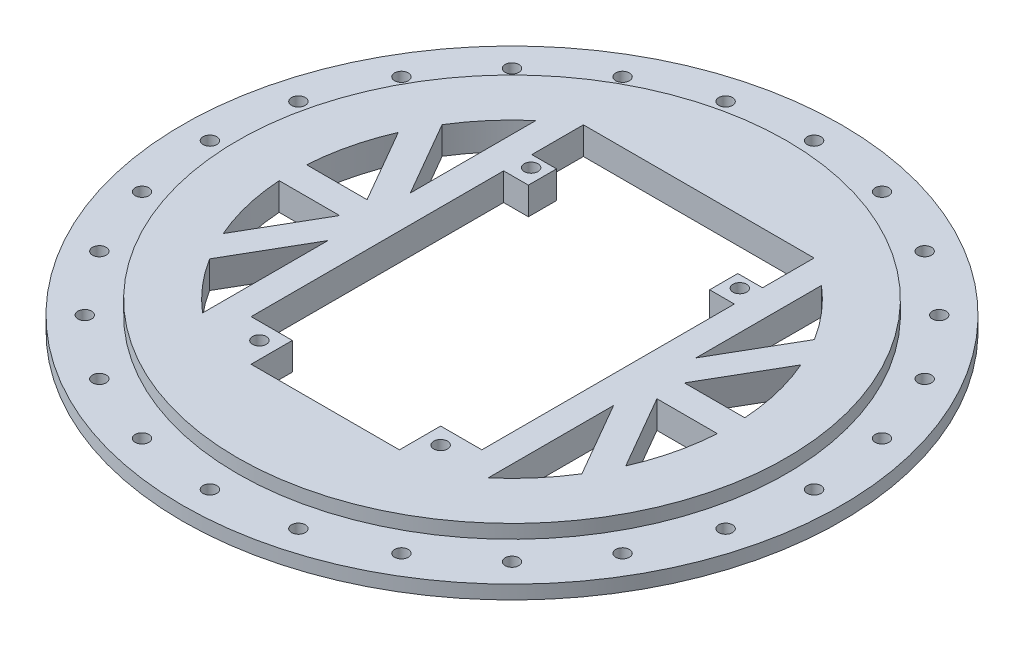
SolidWorks part; units mm, degrees
material "Acrylic (Medium-high impact)"
ref_plane "Front Plane" through (0, 0, 0) normal (0, 0, 1) x (1, 0, 0)
ref_plane "Top Plane" through (0, 0, 0) normal (0, 1, 0) x (1, 0, 0)
ref_plane "Right Plane" through (0, 0, 0) normal (1, 0, 0) x (0, 0, -1)
sketch "Sketch1" plane through (0, 0, 0) normal (0, 1, 0) x (1, 0, 0)
  line L0 (-33.02, -38.5419) -> (-33.02, -9.525)
  line L1 (-17.145, -43.18) -> (17.145, -43.18)
  line L2 (20.955, 31.2547) -> (26.67, 31.2547)
  line L3 (-26.67, 43.18) -> (26.67, 43.18)
  line L4 (17.145, -33.6423) -> (26.67, -33.6423)
  line L5 (33.02, -38.5419) -> (33.02, -9.525)
  line L6 (-33.02, -33.6423) -> (-33.02, 24.7396) construction
  line L7 (26.67, -33.6423) -> (26.67, 24.7396)
  line L8 (20.955, 24.7396) -> (26.67, 24.7396)
  line L9 (20.955, 24.7396) -> (20.955, 31.2547)
  line L10 (33.02, -33.6423) -> (33.02, 24.7396) construction
  line L11 (-33.02, 9.525) -> (-33.02, 38.5419)
  line L12 (33.02, 9.525) -> (33.02, 38.5419)
  line L14 (-36.6862, 3.175) -> (-50.7524, 3.175)
  line L15 (-36.6862, -3.175) -> (-50.7524, -3.175)
  line L16 (-26.67, -33.6423) -> (-17.145, -33.6423)
  line L17 (-17.145, -43.18) -> (-17.145, -33.6423)
  line L18 (17.145, -43.18) -> (17.145, -33.6423)
  line L19 (-26.67, 31.2547) -> (-20.955, 31.2547)
  line L20 (36.6862, 3.175) -> (50.7524, 3.175)
  line L21 (36.6862, -3.175) -> (50.7524, -3.175)
  line L22 (20.955, -37.4523) -> (20.955, 28.5496) construction
  line L23 (-26.67, 24.7396) -> (-20.955, 24.7396)
  line L24 (26.67, 31.2547) -> (26.67, 43.18)
  line L26 (17.145, -37.4523) -> (17.145, 28.5496) construction
  line L27 (-33.02, 9.525) -> (-43.0446, 26.888)
  line L28 (-26.67, 31.2547) -> (-26.67, 43.18)
  line L29 (-36.6862, 3.175) -> (-46.5405, 20.2432)
  line L30 (-26.67, -33.6423) -> (-26.67, 24.7396)
  line L31 (-20.955, 24.7396) -> (-20.955, 31.2547)
  line L33 (36.6862, 3.175) -> (46.5405, 20.2432)
  line L34 (33.02, 9.525) -> (43.0446, 26.888)
  line L35 (-36.6862, -3.175) -> (-46.5405, -20.2432)
  line L36 (-33.02, -9.525) -> (-43.0446, -26.888)
  line L37 (33.02, -9.525) -> (43.0446, -26.888)
  line L38 (36.6862, -3.175) -> (46.5405, -20.2432)
  circle A0 centre (0, 0) radius 76.2
  circle A1 centre (18.0785, 67.4699) radius 1.5875
  circle A2 centre (0, 69.85) radius 1.5875
  circle A3 centre (34.925, 60.4919) radius 1.5875
  circle A4 centre (49.3914, 49.3914) radius 1.5875
  circle A5 centre (60.4919, 34.925) radius 1.5875
  circle A6 centre (67.4699, 18.0785) radius 1.5875
  circle A7 centre (69.85, 0) radius 1.5875
  circle A8 centre (67.4699, -18.0785) radius 1.5875
  circle A9 centre (60.4919, -34.925) radius 1.5875
  circle A10 centre (49.3914, -49.3914) radius 1.5875
  circle A11 centre (34.925, -60.4919) radius 1.5875
  circle A12 centre (18.0785, -67.4699) radius 1.5875
  circle A13 centre (0, -69.85) radius 1.5875
  circle A14 centre (-18.0785, -67.4699) radius 1.5875
  circle A15 centre (-34.925, -60.4919) radius 1.5875
  circle A16 centre (-49.3914, -49.3914) radius 1.5875
  circle A17 centre (-60.4919, -34.925) radius 1.5875
  circle A18 centre (-67.4699, -18.0785) radius 1.5875
  circle A19 centre (-69.85, 0) radius 1.5875
  circle A20 centre (-67.4699, 18.0785) radius 1.5875
  circle A21 centre (-60.4919, 34.925) radius 1.5875
  circle A22 centre (-49.3914, 49.3914) radius 1.5875
  circle A23 centre (-34.925, 60.4919) radius 1.5875
  circle A24 centre (-18.0785, 67.4699) radius 1.5875
  circle A25 centre (-24.13, 28.5496) radius 1.5875
  circle A26 centre (24.13, 28.5496) radius 1.5875
  circle A27 centre (-20.955, -37.4523) radius 1.5875
  circle A28 centre (20.955, -37.4523) radius 1.5875
  circle A29 centre (0, 0) radius 63.5
  arc A30 (-33.02, 38.5419) -> (-43.0446, 26.888) centre (0, 0) ccw
  arc A31 (33.02, -38.5419) -> (43.0446, -26.888) centre (0, 0) ccw
  arc A32 (-50.6529, -3.175) -> (-46.5405, -20.2432) centre (0, 0) ccw
  arc A33 (50.6529, 3.175) -> (46.5405, 20.2432) centre (0, 0) ccw
  arc A34 (-46.5405, 20.2432) -> (-50.6529, 3.175) centre (0, 0) ccw
  arc A35 (-43.0446, -26.888) -> (-33.02, -38.5419) centre (0, 0) ccw
  arc A36 (43.0446, 26.888) -> (33.02, 38.5419) centre (0, 0) ccw
  arc A37 (46.5405, -20.2432) -> (50.6529, -3.175) centre (0, 0) ccw
  dimension "D1" = 24
extrude "Boss-Extrude3" add sketch "Sketch1" along normal blind 6.35 contours A29 A37 L38 L21 A36 L34 L12 A35 L36 L0 A34 L29 L14 A33 L20 L33 A32 L15 L35 A31 L5 L37 A30 L11 L27 L23 L31 L19 L28 L3 L24 L2 L9 L8 region at (-61.7039, 0, 0)
extrude "Boss-Extrude4" add sketch "Sketch1<7>" along normal blind 3.175 contours A0 A29 A24 A23 A22 A21 A20 A19 A18 A17 A16 A15 A14 A13 A12 A11 A10 A9 A8 A7 A6 A5 A4 A3 A2 A1 region at (-74.0447, 0, 0)
sketch "Sketch1<7>" plane through (0, 0, 0) normal (0, 1, 0) x (1, 0, 0) same geometry as "Sketch1"
